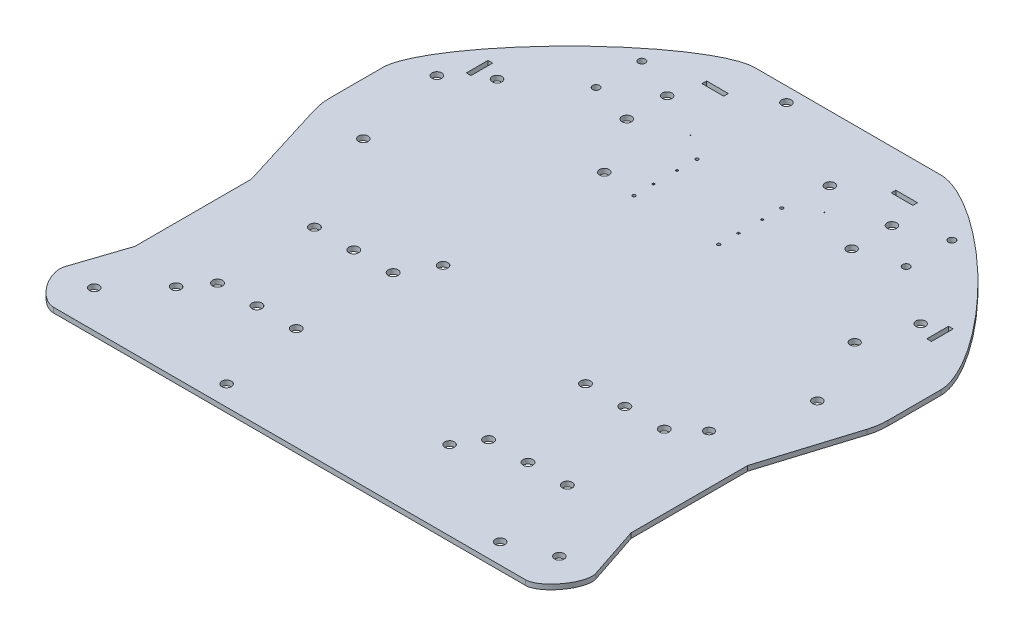
SolidWorks part; units mm, degrees
ref_plane "Front Plane" through (0, 0, 0) normal (0, 0, 1) x (1, 0, 0)
ref_plane "Top Plane" through (0, 0, 0) normal (0, 1, 0) x (1, 0, 0)
ref_plane "Right Plane" through (0, 0, 0) normal (1, 0, 0) x (0, 0, -1)
sketch "Sketch1" plane through (0, 0, 0) normal (0, 1, 0) x (1, 0, 0)
  line L0 (-90, 180) -> (-90, 0) construction
  line L1 (-180, 180) -> (0, 180)
  line L2 (-180, 180) -> (-180, 0)
  line L3 (-180, 0) -> (0, 0)
  line L4 (0, 180) -> (0, 0)
  line L5 (-180, 90) -> (0, 90) construction
  line L6 (-180, 30) -> (0, 30)
  line L7 (-130, 30) -> (-50, 30)
  line L8 (-130, 30) -> (-130, -30)
  line L9 (-130, -30) -> (-50, -30)
  line L10 (-50, 30) -> (-50, -30)
  line L11 (-130, 30) -> (-50, -30) construction
  line L12 (-130, -30) -> (-50, 30) construction
  dimension "D1" = 180
  dimension "D2" = 180
  dimension "D3" = 60
  dimension "D4" = 80
extrude "Boss-Extrude1" add sketch "Sketch1" along normal blind 1.6 contours L10 L3 L8 L9 | L2 L6 L4 L1 | L6 L10 L3 L4 | L8 L6 L2 L3 | L10 L6 L8 L3 region at (-90, 0, -105) region at (-155, 0, -15) region at (-25, 0, -15) region at (-90, 0, -15) region at (-90, 0, 15)
sketch "Sketch2" plane through (0, 1.6, 0) normal (0, 1, 0) x (1, 0, 0)
  line L0 (-180, 30) -> (0, 30)
  line L1 (-180, 180) -> (-180, 0) construction
  line L2 (0, 180) -> (0, 0) construction
  line L3 (-180, 180) -> (0, 180) construction
  line L4 (-90, 180) -> (-90, -30) construction
  line L5 (-130, -30) -> (-50, -30) construction
  dimension "D1" = 150
sketch "Sketch3" plane through (0, 1.6, 0) normal (0, 1, 0) x (1, 0, 0)
  line L0 (-180, 122) -> (0, 122)
  line L1 (-180, 180) -> (-180, 0) construction
  line L2 (0, 180) -> (0, 0) construction
  line L3 (-180, 30) -> (0, 30) construction
  dimension "D1" = 92
sketch "Sketch5" plane through (0, 1.6, 0) normal (0, 1, 0) x (1, 0, 0)
  line L0 (-114, 180) -> (-114, -30)
  line L1 (-180, 180) -> (0, 180) construction
  line L2 (-130, -30) -> (-50, -30) construction
  line L3 (-90, 180) -> (-90, -30) construction
  dimension "D1" = 24
fillet "Fillet1" radius 60 2 edges at (0, 0.8, -180) (-180, 0.8, -180) conic rho 0.2
sketch "Sketch6" plane through (0, 1.6, 0) normal (0, 1, 0) x (1, 0, 0)
  line L0 (-50, 0) -> (-130, 0)
  line L1 (-130, 0) -> (-130, -30)
  line L2 (-130, -30) -> (-50, -30)
  line L3 (-50, -30) -> (-50, 0)
  line L4 (-180, 0) -> (-170, 30.1113)
  line L5 (-170, 30.1113) -> (-170, 67.7113)
  line L6 (-170, 67.7113) -> (-180, 100)
  line L7 (-180, 120) -> (-180, 0) construction
  line L8 (-90, 180) -> (-90, -30) construction
  line L10 (-90, 180) -> (-90, 0) construction
  line L11 (0, 0) -> (-10, 30.1113)
  line L12 (-10, 30.1113) -> (-10, 67.7113)
  line L13 (-10, 67.7113) -> (0, 100)
  line M3 (0, 0) -> (0, 120)
  line M7 (-180, 120) -> (-180, 0)
  line M9 (-130, 0) -> (-130, -30)
  line M10 (-130, -30) -> (-50, -30)
  line M11 (-50, -30) -> (-50, 0)
  dimension "D1" = 37.6
  dimension "D2" = 80
  dimension "D3" = 100
extrude "Cut-Extrude1" cut sketch "Sketch6" against normal blind 10 contours L0 M11 M9 M10 | L5 L6 L4 M7 | L13 L12 L11 M3 region at (-90, 1.6, 15) region at (-175.7558, 1.6, -49.5379) region at (-4.2442, 1.6, -49.5379)
fillet "Fillet2" radius 10 2 edges at (-180, 0.8, 0) (0, 0.8, 0) conic rho 0.25
fillet "Fillet3" radius 20 2 edges at (-180, 0.8, -100) (0, 0.8, -100)
sketch "Sketch8" plane through (0, 1.6, 0) normal (0, 1, 0) x (1, 0, 0)
  line L1 (-63, 168.5) -> (-56, 168.5)
  line L2 (-63, 168.5) -> (-63, 167)
  line L3 (-63, 167) -> (-56, 167)
  line L4 (-56, 168.5) -> (-56, 167)
  line L5 (-117, 168.5) -> (-124, 168.5)
  line L6 (-117, 168.5) -> (-117, 167)
  line L7 (-117, 167) -> (-124, 167)
  line L8 (-124, 168.5) -> (-124, 167)
  line L9 (-165, 139) -> (-163.5, 139)
  line L10 (-165, 139) -> (-165, 132)
  line L11 (-165, 132) -> (-163.5, 132)
  line L12 (-163.5, 139) -> (-163.5, 132)
  line L13 (-16.5, 139) -> (-15, 139)
  line L14 (-16.5, 139) -> (-16.5, 132)
  line L15 (-16.5, 132) -> (-15, 132)
  line L16 (-15, 139) -> (-15, 132)
  circle A4 centre (-105.105, 175.3311) radius 1.55
  circle A5 centre (-74.9002, 159.1312) radius 1.55
  circle A8 centre (-115, 74.5) radius 1.55
  circle A9 centre (-115, 126.5) radius 1.55
  circle A11 centre (-146.4125, 64.417) radius 1.5875
  circle A12 centre (-133.7125, 64.417) radius 1.5875
  circle A13 centre (-121.0125, 64.417) radius 1.5875
  circle A14 centre (-146.4125, 33.175) radius 1.5875
  circle A15 centre (-133.7125, 33.175) radius 1.5875
  circle A16 centre (-121.0125, 33.175) radius 1.5875
  circle A17 centre (-58.9875, 64.417) radius 1.5875
  circle A18 centre (-46.2875, 64.417) radius 1.5875
  circle A19 centre (-33.5875, 64.417) radius 1.5875
  circle A20 centre (-33.5875, 33.175) radius 1.5875
  circle A21 centre (-46.2875, 33.175) radius 1.5875
  circle A22 centre (-58.9875, 33.175) radius 1.5875
  circle A23 centre (-63.9, 25.5) radius 1.55
  circle A24 centre (-28.6, 6.5) radius 1.55
  circle A25 centre (-116.8, 6.5) radius 1.55
  circle A26 centre (-152.1, 25.5) radius 1.55
  circle A27 centre (-27.14, 119.392) radius 1.5
  circle A28 centre (-25.87, 71.132) radius 1.5
  circle A29 centre (-169, 126.5) radius 1.55
  circle A30 centre (-126.25, 145) radius 1.55
  circle A31 centre (-53.75, 145) radius 1.55
  circle A32 centre (-165, 12) radius 1.55
  circle A33 centre (-15, 12) radius 1.55
  dimension "D3" = 3.1
  dimension "D4" = 3.1
  dimension "D5" = 3.1
  dimension "D6" = 3.1
  dimension "D7" = 3.1
  dimension "D8" = 3.175
  dimension "D9" = 3.175
  dimension "D10" = 3.175
  dimension "D11" = 3.175
  dimension "D12" = 3.175
  dimension "D13" = 3.175
  dimension "D14" = 3.1
  dimension "D15" = 3.1
  dimension "D16" = 3.1
  dimension "D17" = 3.1
  dimension "D18" = 3.175
  dimension "D19" = 3.175
  dimension "D20" = 3.175
  dimension "D21" = 3.175
  dimension "D22" = 3.175
  dimension "D23" = 3.175
  dimension "D24" = 3
  dimension "D25" = 3
  dimension "D26" = 3.1
  dimension "D27" = 3.1
  dimension "D28" = 3.1
  dimension "D29" = 3.1
extrude "Cut-Extrude2" cut sketch "Sketch8" against normal up to next (1.6 mm away)
sketch "Sketch9" plane through (0, 0, 0) normal (0, -1, 0) x (1, 0, 0)
  line L1 (-68.18, -150.89) -> (-68.42, -150.89)
  line L2 (-68.18, -150.89) -> (-68.18, -150.65)
  line L3 (-68.18, -150.65) -> (-68.42, -150.65)
  line L4 (-68.42, -150.89) -> (-68.42, -150.65)
  line L5 (-111.36, -150.89) -> (-111.6, -150.89)
  line L6 (-111.36, -150.89) -> (-111.36, -150.65)
  line L7 (-111.36, -150.65) -> (-111.6, -150.65)
  line L8 (-111.6, -150.89) -> (-111.6, -150.65)
  line L9 (-76.01, -139.0625) -> (-76.645, -139.0625)
  line L10 (-76.01, -139.0625) -> (-76.01, -138.4275)
  line L11 (-76.01, -138.4275) -> (-76.645, -138.4275)
  line L12 (-76.645, -139.0625) -> (-76.645, -138.4275)
  line L13 (-76.01, -131.4425) -> (-76.645, -131.4425)
  line L14 (-76.01, -131.4425) -> (-76.01, -130.8075)
  line L15 (-76.01, -130.8075) -> (-76.645, -130.8075)
  line L16 (-76.645, -131.4425) -> (-76.645, -130.8075)
  line L17 (-103.47, -139.0625) -> (-104.105, -139.0625)
  line L18 (-103.47, -139.0625) -> (-103.47, -138.4275)
  line L19 (-103.47, -138.4275) -> (-104.105, -138.4275)
  line L20 (-104.105, -139.0625) -> (-104.105, -138.4275)
  line L21 (-103.47, -131.4425) -> (-104.105, -131.4425)
  line L22 (-103.47, -131.4425) -> (-103.47, -130.8075)
  line L23 (-103.47, -130.8075) -> (-104.105, -130.8075)
  line L24 (-104.105, -131.4425) -> (-104.105, -130.8075)
  circle A0 centre (-163.2, -97) radius 1.55
  circle A1 centre (-158.3, -135.2) radius 1.55
  circle A2 centre (-126.25, -158) radius 1.55
  circle A3 centre (-53.75, -158) radius 1.55
  circle A4 centre (-21.7, -135.2) radius 1.55
  circle A5 centre (-16.8, -97) radius 1.55
  circle A6 centre (-76.405, -124.775) radius 0.5
  circle A7 centre (-103.71, -145.095) radius 0.5
  circle A8 centre (-76.405, -145.095) radius 0.5
  circle A9 centre (-103.71, -124.775) radius 0.5
  circle A10 centre (-140, -148.857) radius 1.143
  circle A11 centre (-140, -163.589) radius 1.143
  circle A12 centre (-40, -148.857) radius 1.143
  circle A13 centre (-40, -163.589) radius 1.143
  dimension "D1" = 3.1
  dimension "D2" = 3.1
  dimension "D3" = 3.1
  dimension "D4" = 3.1
  dimension "D5" = 3.1
  dimension "D6" = 3.1
  dimension "D7" = 1
  dimension "D8" = 1
  dimension "D9" = 1
  dimension "D10" = 1
  dimension "D11" = 2.286
  dimension "D12" = 2.286
  dimension "D13" = 2.286
  dimension "D14" = 2.286
extrude "Cut-Extrude3" cut sketch "Sketch9" against normal up to next
